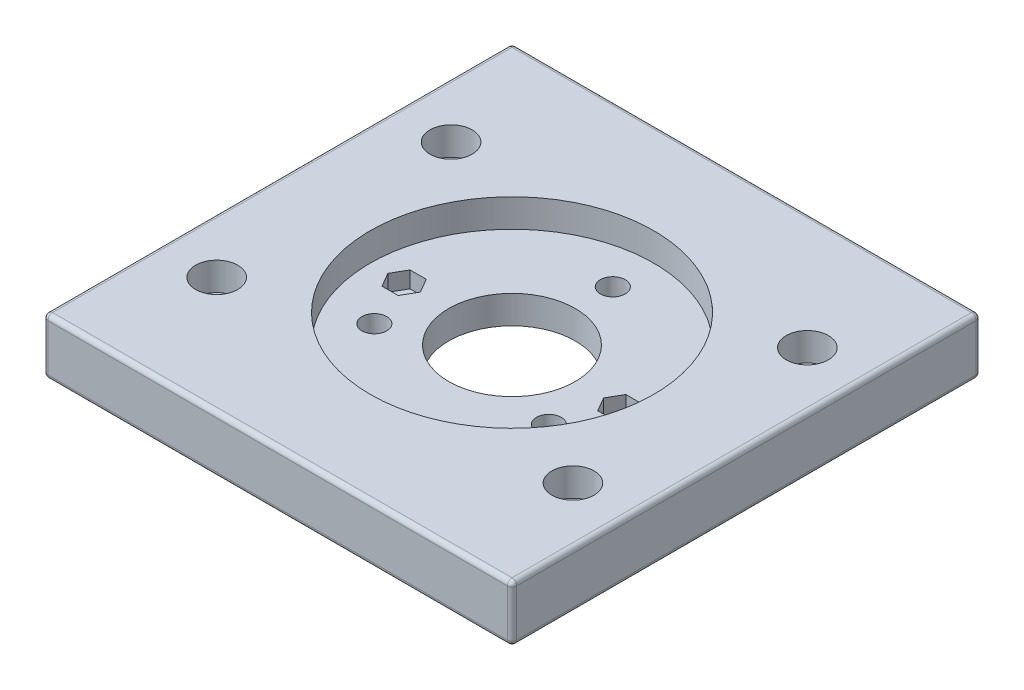
SolidWorks part; units mm, degrees
ref_plane "Front Plane" through (0, 0, 0) normal (0, 0, 1) x (1, 0, 0)
ref_plane "Top Plane" through (0, 0, 0) normal (0, 1, 0) x (1, 0, 0)
ref_plane "Right Plane" through (0, 0, 0) normal (1, 0, 0) x (0, 0, -1)
sketch "Sketch1" plane through (0, 0, 0) normal (0, 1, 0) x (1, 0, 0)
  line L0 (0, 0) -> (0, 21.5) construction
  line L1 (0, 0) -> (23.0125, 0) construction
  line L3 (50, 50) -> (-50, 50)
  line L4 (50, 50) -> (50, -50)
  line L5 (50, -50) -> (-50, -50)
  line L6 (-50, 50) -> (-50, -50)
  circle A0 centre (0, 0) radius 13.5
  circle A1 centre (0, 0) radius 23.0125 construction
  circle A2 centre (0, 0) radius 21.5 construction
  circle A4 centre (0, 21.5) radius 2.65
  circle A5 centre (23.0125, 0) radius 1.65
  circle A6 centre (-23.0125, 0) radius 1.65
  circle A7 centre (18.6195, -10.75) radius 2.65
  circle A8 centre (-18.6195, -10.75) radius 2.65
  circle A13 centre (-38, 25) radius 1.75
  circle A14 centre (-38, -25) radius 1.75
  circle A15 centre (38, -25) radius 1.75
  circle A16 centre (38, 25) radius 1.75
  point P24 (-50, 0)
  point P25 (0, 50)
  dimension "D1" = 27
  dimension "D2" = 46.025
  dimension "D3" = 43
  dimension "D4" = 3.5
  dimension "D5" = 5.3
  dimension "D6" = 3.3
  dimension "D9" = 25
  dimension "D10" = 38
  dimension "D12" = 100
  dimension "D13" = 100
  dimension "D7" = 2
  dimension "D8" = 3
extrude "Boss-Extrude1" add sketch "Sketch1" along normal blind 6
ref_plane "Plane4" through (0, 6, 0) normal (0, 1, 0) x (1, 0, 0)
ref_plane "Plane6" through (0, 6, 0) normal (0, 1, 0) x (1, 0, 0)
sketch "Sketch8" plane through (0, 6, 0) normal (0, 1, 0) x (1, 0, 0)
  line L0 (19.5484, 0) -> (21.2804, -3)
  line L1 (-19.5484, 0) -> (-21.2804, 3)
  line L2 (-21.2804, 3) -> (-24.7446, 3)
  line L3 (-24.7446, 3) -> (-26.4766, 0)
  line L4 (-26.4766, 0) -> (-24.7446, -3)
  line L5 (-24.7446, -3) -> (-21.2804, -3)
  line L6 (-21.2804, -3) -> (-19.5484, 0)
  line L7 (21.2804, -3) -> (24.7446, -3)
  line L8 (24.7446, -3) -> (26.4766, 0)
  line L9 (26.4766, 0) -> (24.7446, 3)
  line L10 (24.7446, 3) -> (21.2804, 3)
  line L11 (21.2804, 3) -> (19.5484, 0)
  circle A0 centre (-23.0125, 0) radius 1.65 construction
  circle A1 centre (-23.0125, 0) radius 1.65 construction
  circle A2 centre (0, 0) radius 23.0125 construction
  circle A3 centre (-23.0125, 0) radius 3 construction
  point P6 (-23.0125, 3)
  dimension "D1" = 6
  dimension "D2" = 2
extrude "Cut-Extrude2" cut sketch "Sketch8" against normal blind 3.5
sketch "Sketch9" plane through (0, 6, 0) normal (0, 1, 0) x (1, 0, 0)
  line L0 (-50, 50) -> (-50, -50) construction
  line L1 (50, 50) -> (-50, 50) construction
  line L2 (50, -50) -> (50, 50) construction
  line L3 (-50, -50) -> (50, -50) construction
  line L4 (-50, 50) -> (-50, -50)
  line L5 (50, 50) -> (-50, 50)
  line L6 (50, -50) -> (50, 50)
  line L7 (-50, -50) -> (50, -50)
  circle A0 centre (0, 0) radius 30.25
  circle A1 centre (38, 25) radius 1.75 construction
  circle A2 centre (38, -25) radius 1.75 construction
  circle A3 centre (-38, -25) radius 1.75 construction
  circle A4 centre (-38, 25) radius 1.75 construction
  circle A5 centre (38, 25) radius 1.75 construction
  circle A6 centre (38, -25) radius 1.75 construction
  circle A7 centre (-38, -25) radius 1.75 construction
  circle A8 centre (-38, 25) radius 1.75 construction
  circle A9 centre (-38, 25) radius 4.5
  circle A10 centre (-38, -25) radius 4.5
  circle A11 centre (38, -25) radius 4.5
  circle A12 centre (38, 25) radius 4.5
  dimension "D1" = 60.5
  dimension "D2" = 9
extrude "Boss-Extrude2" add sketch "Sketch9" along normal blind 6
fillet "Fillet1" radius 1 12 edges at (50, 6, 50) (50, 12, 0) (50, 0, 0) (-50, 12, 0) (-50, 6, 50) (-50, 0, 0) (50, 6, -50) (0, 12, -50) (-50, 6, -50) (0, 0, -50) (0, 0, 50) (0, 12, 50)
